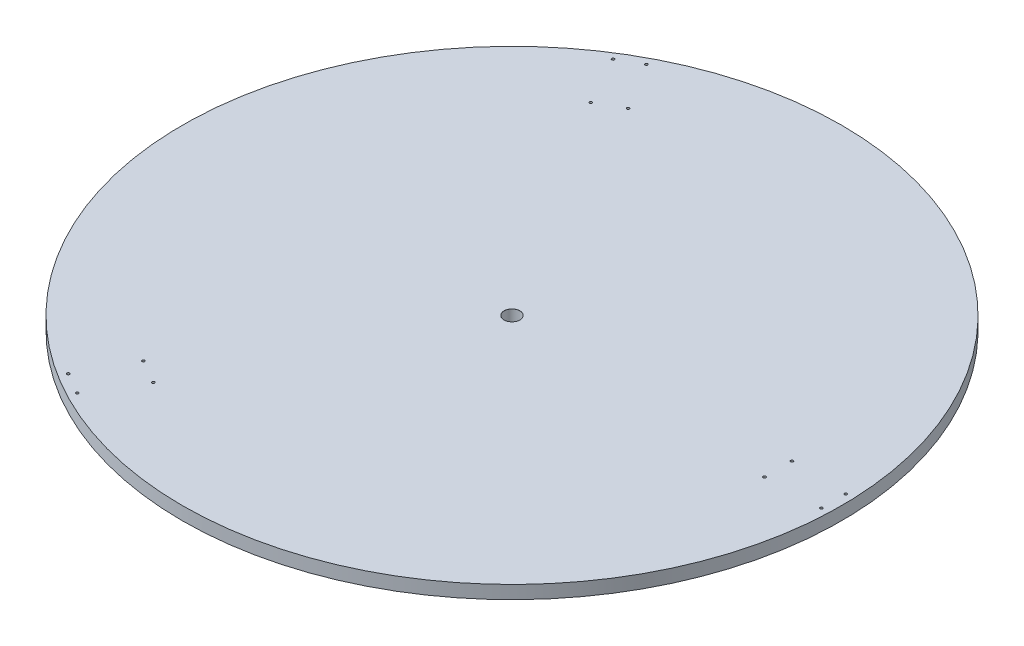
SolidWorks part; units mm, degrees
ref_plane "Plan de face" through (0, 0, 0) normal (0, 0, 1) x (1, 0, 0)
ref_plane "Plan de dessus" through (0, 0, 0) normal (0, 1, 0) x (1, 0, 0)
ref_plane "Plan de droite" through (0, 0, 0) normal (1, 0, 0) x (0, 0, -1)
sketch "Esquisse1" plane through (0, 0, 0) normal (0, 1, 0) x (1, 0, 0)
  circle A0 centre (0, 0) radius 250
  dimension "D1" = 500
extrude "Boss.-Extru.1" add sketch "Esquisse1" along normal mid plane 10
sketch "Esquisse5" plane through (0, 5, 0) normal (0, 1, 0) x (1, 0, 0)
  point P0 (0, 0)
hole_wizard "Dégagement M101" positions "Esquisse5" profile "Esquisse4" hole size "M10" standard "ISO" end condition through all
sketch "Esquisse4" plane through (0, 5, 0) normal (1, 0, 0) x (0, 0, 1)
  line L0 (0, 0) -> (0, 10)
  line L1 (0, 10) -> (6, 10)
  line L2 (6, 10) -> (6, 0.025)
  line L3 (6, 0.025) -> (6.025, 0)
  line L5 (6.025, 0) -> (0, 0)
  line L6 (-6, 0.025) -> (-6.025, 0) construction
  line L11 (0, -6.35) -> (0, 107.95) construction
  dimension "Diamètre du perçage jusqu'au prochain" = 12
  dimension "Profondeur du perçage jusqu'au prochain" = 10
  dimension "Diamètre du fraisage entrant" = 12.05
  dimension "Angle du fraisage entrant" = 90
sketch "Esquisse6" plane through (0, 5, 0) normal (0, 1, 0) x (1, 0, 0)
  line L0 (0, 0) -> (349.9995, 0) construction
  line L1 (0, 0) -> (-167.1022, 289.4294) construction
  line L2 (0, 0) -> (-171.7601, -297.4973) construction
  line L3 (243.9544, 9.25) -> (243.9544, -9.25) construction
  circle A0 centre (243.9544, 9.25) radius 1
  circle A1 centre (243.9544, -9.25) radius 1
  circle A2 centre (201.9502, 10.4) radius 1
  circle A3 centre (201.9502, -10.4) radius 1
  dimension "D5" = 2
  dimension "D6" = 2
  dimension "D7" = 243.9544
  dimension "D9" = 2
  dimension "D1" = 120
  dimension "D2" = 120
  dimension "D3" = 9.25
  dimension "D4" = 9.25
  dimension "D8" = 42.02
  dimension "D10" = 10.4
extrude "Enlèv. mat.-Extru.1" cut sketch "Esquisse6" against normal through all
pattern_circular "Répétition circulaire1" count 3 over 360 about axis through (0, 5, 0) along (0, 1, 0) of "Enlèv. mat.-Extru.1" reverse direction yes
